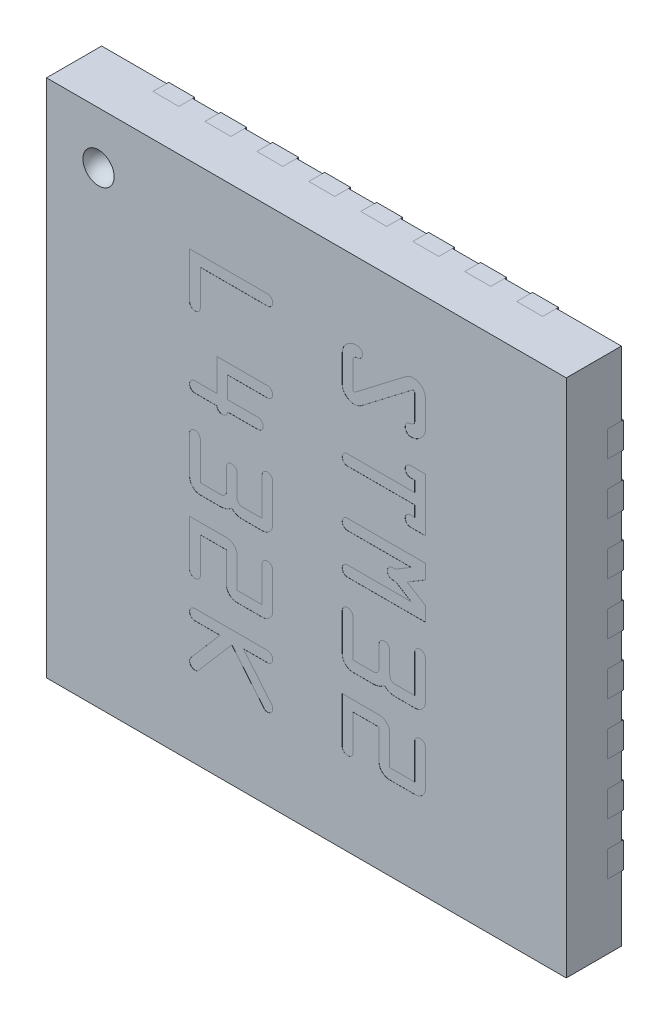
SolidWorks part; units mm, degrees
ref_plane "Спереди" through (0, 0, 0) normal (0, 0, 1) x (1, 0, 0)
ref_plane "Сверху" through (0, 0, 0) normal (0, 1, 0) x (1, 0, 0)
ref_plane "Справа" through (0, 0, 0) normal (1, 0, 0) x (0, 0, -1)
ref_plane "Плоскость1" through (0, 0, 0.02) normal (0, 0, 1) x (1, 0, 0)
sketch "Эскиз2" plane through (0, 0, 0.02) normal (0, 0, 1) x (1, 0, 0)
  line L1 (-2.5, -2.5) -> (2.5, -2.5)
  line L2 (-2.5, -2.5) -> (-2.5, 2.5)
  line L3 (-2.5, 2.5) -> (2.5, 2.5)
  line L4 (2.5, -2.5) -> (2.5, 2.5)
  line L5 (-2.5, -2.5) -> (2.5, 2.5) construction
  line L6 (-2.5, 2.5) -> (2.5, -2.5) construction
  point P0 (0, 0)
  dimension "D1" = 5
extrude "Бобышка-Вытянуть2" add sketch "Эскиз2" along normal blind 0.53 separate body
sketch "Эскиз1" plane through (0, 0, 0) normal (0, 0, 1) x (1, 0, 0)
  line L0 (0.125, 2.1) -> (0.375, 2.1) construction
  line L1 (-2.5, -2.5) -> (2.5, -2.5) construction
  line L2 (-2.5, -2.5) -> (-2.5, 2.5) construction
  line L3 (-2.5, 2.5) -> (2.5, 2.5) construction
  line L4 (2.5, -2.5) -> (2.5, 2.5) construction
  line L5 (-2.5, -2.5) -> (2.5, 2.5) construction
  line L6 (-2.5, 2.5) -> (2.5, -2.5) construction
  line L7 (0.625, 2.225) -> (0.625, 2.5)
  line L8 (0.125, 2.225) -> (0.125, 2.5)
  line L9 (0.125, 2.5) -> (0.375, 2.5)
  line L10 (0.375, 2.225) -> (0.375, 2.5)
  line L11 (0.125, 2.1) -> (0.375, 2.5) construction
  line L12 (0.125, 2.5) -> (0.375, 2.1) construction
  line L13 (0.625, 2.5) -> (0.875, 2.5)
  line L14 (0.875, 2.225) -> (0.875, 2.5)
  line L15 (0.625, 2.1) -> (0.875, 2.1) construction
  line L16 (0.625, 2.1) -> (0.875, 2.5) construction
  line L17 (0.625, 2.5) -> (0.875, 2.1) construction
  line L18 (1.125, 2.225) -> (1.125, 2.5)
  line L19 (1.125, 2.5) -> (1.375, 2.5)
  line L20 (1.375, 2.225) -> (1.375, 2.5)
  line L21 (1.125, 2.1) -> (1.375, 2.1) construction
  line L22 (1.125, 2.1) -> (1.375, 2.5) construction
  line L23 (1.125, 2.5) -> (1.375, 2.1) construction
  line L24 (1.625, 2.225) -> (1.625, 2.5)
  line L25 (1.625, 2.5) -> (1.875, 2.5)
  line L26 (1.875, 2.225) -> (1.875, 2.5)
  line L27 (1.625, 2.1) -> (1.875, 2.1) construction
  line L28 (1.625, 2.1) -> (1.875, 2.5) construction
  line L29 (1.625, 2.5) -> (1.875, 2.1) construction
  line L30 (2.225, -0.625) -> (2.5, -0.625)
  line L31 (2.225, -0.125) -> (2.5, -0.125)
  line L32 (2.5, -0.125) -> (2.5, -0.375)
  line L33 (2.225, -0.375) -> (2.5, -0.375)
  line L34 (2.5, -0.625) -> (2.5, -0.875)
  line L35 (2.225, -0.875) -> (2.5, -0.875)
  line L36 (2.225, -1.125) -> (2.5, -1.125)
  line L37 (2.5, -1.125) -> (2.5, -1.375)
  line L38 (2.225, -1.375) -> (2.5, -1.375)
  line L39 (2.225, -1.625) -> (2.5, -1.625)
  line L40 (2.5, -1.625) -> (2.5, -1.875)
  line L41 (2.225, -1.875) -> (2.5, -1.875)
  line L42 (0, -1000) -> (0, 49000) construction
  line L43 (-1000, 0) -> (49000, 0) construction
  line L44 (2.225, 1.875) -> (2.5, 1.875)
  line L45 (2.5, 1.625) -> (2.5, 1.875)
  line L46 (2.225, 1.625) -> (2.5, 1.625)
  line L47 (2.225, 1.375) -> (2.5, 1.375)
  line L48 (2.5, 1.125) -> (2.5, 1.375)
  line L49 (2.225, 1.125) -> (2.5, 1.125)
  line L50 (-1.625, 2.5) -> (-1.875, 2.1) construction
  line L51 (-1.625, 2.1) -> (-1.875, 2.5) construction
  line L52 (-1.625, 2.1) -> (-1.875, 2.1) construction
  line L53 (-1.125, 2.5) -> (-1.375, 2.1) construction
  line L54 (-1.125, 2.1) -> (-1.375, 2.5) construction
  line L55 (-1.125, 2.1) -> (-1.375, 2.1) construction
  line L56 (-0.625, 2.5) -> (-0.875, 2.1) construction
  line L57 (-0.625, 2.1) -> (-0.875, 2.5) construction
  line L58 (-0.625, 2.1) -> (-0.875, 2.1) construction
  line L59 (-0.125, 2.5) -> (-0.375, 2.1) construction
  line L60 (-0.125, 2.1) -> (-0.375, 2.5) construction
  line L61 (-0.125, 2.1) -> (-0.375, 2.1) construction
  line L62 (2.225, 0.875) -> (2.5, 0.875)
  line L63 (2.5, 0.625) -> (2.5, 0.875)
  line L64 (2.225, 0.375) -> (2.5, 0.375)
  line L65 (2.5, 0.125) -> (2.5, 0.375)
  line L66 (2.225, 0.125) -> (2.5, 0.125)
  line L67 (2.225, 0.625) -> (2.5, 0.625)
  line L68 (-1.875, 2.225) -> (-1.875, 2.5)
  line L69 (-1.625, 2.5) -> (-1.875, 2.5)
  line L70 (-1.625, 2.225) -> (-1.625, 2.5)
  line L71 (-1.375, 2.225) -> (-1.375, 2.5)
  line L72 (-1.125, 2.5) -> (-1.375, 2.5)
  line L73 (-1.125, 2.225) -> (-1.125, 2.5)
  line L74 (-0.875, 2.225) -> (-0.875, 2.5)
  line L75 (-0.625, 2.5) -> (-0.875, 2.5)
  line L76 (-0.375, 2.225) -> (-0.375, 2.5)
  line L77 (-0.125, 2.5) -> (-0.375, 2.5)
  line L78 (-0.125, 2.225) -> (-0.125, 2.5)
  line L79 (-0.625, 2.225) -> (-0.625, 2.5)
  line L80 (2.1, -0.125) -> (2.1, -0.375) construction
  line L81 (2.1, -0.125) -> (2.5, -0.375) construction
  line L82 (2.5, -0.125) -> (2.1, -0.375) construction
  line L83 (2.1, -0.625) -> (2.1, -0.875) construction
  line L84 (2.1, -0.625) -> (2.5, -0.875) construction
  line L85 (2.5, -0.625) -> (2.1, -0.875) construction
  line L86 (2.1, -1.125) -> (2.1, -1.375) construction
  line L87 (2.1, -1.125) -> (2.5, -1.375) construction
  line L88 (2.5, -1.125) -> (2.1, -1.375) construction
  line L89 (2.1, -1.625) -> (2.1, -1.875) construction
  line L90 (2.1, -1.625) -> (2.5, -1.875) construction
  line L91 (2.5, -1.625) -> (2.1, -1.875) construction
  line L92 (2.5, 1.625) -> (2.1, 1.875) construction
  line L93 (2.1, 1.625) -> (2.5, 1.875) construction
  line L94 (2.1, 1.625) -> (2.1, 1.875) construction
  line L95 (2.5, 1.125) -> (2.1, 1.375) construction
  line L96 (2.1, 1.125) -> (2.5, 1.375) construction
  line L97 (2.1, 1.125) -> (2.1, 1.375) construction
  line L98 (2.5, 0.625) -> (2.1, 0.875) construction
  line L99 (2.1, 0.625) -> (2.5, 0.875) construction
  line L100 (2.1, 0.625) -> (2.1, 0.875) construction
  line L101 (2.5, 0.125) -> (2.1, 0.375) construction
  line L102 (2.1, 0.125) -> (2.5, 0.375) construction
  line L103 (2.1, 0.125) -> (2.1, 0.375) construction
  line L104 (-0.625, -2.225) -> (-0.625, -2.5)
  line L105 (-0.125, -2.225) -> (-0.125, -2.5)
  line L106 (-0.125, -2.5) -> (-0.375, -2.5)
  line L107 (-0.375, -2.225) -> (-0.375, -2.5)
  line L108 (-0.625, -2.5) -> (-0.875, -2.5)
  line L109 (-0.875, -2.225) -> (-0.875, -2.5)
  line L110 (-1.125, -2.225) -> (-1.125, -2.5)
  line L111 (-1.125, -2.5) -> (-1.375, -2.5)
  line L112 (-1.375, -2.225) -> (-1.375, -2.5)
  line L113 (-1.625, -2.225) -> (-1.625, -2.5)
  line L114 (-1.625, -2.5) -> (-1.875, -2.5)
  line L115 (-1.875, -2.225) -> (-1.875, -2.5)
  line L116 (1.875, -2.225) -> (1.875, -2.5)
  line L117 (1.625, -2.5) -> (1.875, -2.5)
  line L118 (1.625, -2.225) -> (1.625, -2.5)
  line L119 (1.375, -2.225) -> (1.375, -2.5)
  line L120 (1.125, -2.5) -> (1.375, -2.5)
  line L121 (1.125, -2.225) -> (1.125, -2.5)
  line L122 (0.875, -2.225) -> (0.875, -2.5)
  line L123 (0.625, -2.5) -> (0.875, -2.5)
  line L124 (0.375, -2.225) -> (0.375, -2.5)
  line L125 (0.125, -2.5) -> (0.375, -2.5)
  line L126 (0.125, -2.225) -> (0.125, -2.5)
  line L127 (0.625, -2.225) -> (0.625, -2.5)
  line L128 (-0.125, -2.1) -> (-0.375, -2.1) construction
  line L129 (-0.125, -2.1) -> (-0.375, -2.5) construction
  line L130 (-0.125, -2.5) -> (-0.375, -2.1) construction
  line L131 (-0.625, -2.1) -> (-0.875, -2.1) construction
  line L132 (-0.625, -2.1) -> (-0.875, -2.5) construction
  line L133 (-0.625, -2.5) -> (-0.875, -2.1) construction
  line L134 (-1.125, -2.1) -> (-1.375, -2.1) construction
  line L135 (-1.125, -2.1) -> (-1.375, -2.5) construction
  line L136 (-1.125, -2.5) -> (-1.375, -2.1) construction
  line L137 (-1.625, -2.1) -> (-1.875, -2.1) construction
  line L138 (-1.625, -2.1) -> (-1.875, -2.5) construction
  line L139 (-1.625, -2.5) -> (-1.875, -2.1) construction
  line L140 (1.625, -2.5) -> (1.875, -2.1) construction
  line L141 (1.625, -2.1) -> (1.875, -2.5) construction
  line L142 (1.625, -2.1) -> (1.875, -2.1) construction
  line L143 (1.125, -2.5) -> (1.375, -2.1) construction
  line L144 (1.125, -2.1) -> (1.375, -2.5) construction
  line L145 (1.125, -2.1) -> (1.375, -2.1) construction
  line L146 (0.625, -2.5) -> (0.875, -2.1) construction
  line L147 (0.625, -2.1) -> (0.875, -2.5) construction
  line L148 (0.625, -2.1) -> (0.875, -2.1) construction
  line L149 (0.125, -2.5) -> (0.375, -2.1) construction
  line L150 (0.125, -2.1) -> (0.375, -2.5) construction
  line L151 (0.125, -2.1) -> (0.375, -2.1) construction
  line L152 (-2.225, 0.625) -> (-2.5, 0.625)
  line L153 (-2.225, 0.125) -> (-2.5, 0.125)
  line L154 (-2.5, 0.125) -> (-2.5, 0.375)
  line L155 (-2.225, 0.375) -> (-2.5, 0.375)
  line L156 (-2.5, 0.625) -> (-2.5, 0.875)
  line L157 (-2.225, 0.875) -> (-2.5, 0.875)
  line L158 (-2.225, 1.125) -> (-2.5, 1.125)
  line L159 (-2.5, 1.125) -> (-2.5, 1.375)
  line L160 (-2.225, 1.375) -> (-2.5, 1.375)
  line L161 (-2.225, 1.625) -> (-2.5, 1.625)
  line L162 (-2.5, 1.625) -> (-2.5, 1.875)
  line L163 (-2.225, 1.875) -> (-2.5, 1.875)
  line L164 (-2.225, -1.875) -> (-2.5, -1.875)
  line L165 (-2.5, -1.625) -> (-2.5, -1.875)
  line L166 (-2.225, -1.625) -> (-2.5, -1.625)
  line L167 (-2.225, -1.375) -> (-2.5, -1.375)
  line L168 (-2.5, -1.125) -> (-2.5, -1.375)
  line L169 (-2.225, -1.125) -> (-2.5, -1.125)
  line L170 (-2.225, -0.875) -> (-2.5, -0.875)
  line L171 (-2.5, -0.625) -> (-2.5, -0.875)
  line L172 (-2.225, -0.375) -> (-2.5, -0.375)
  line L173 (-2.5, -0.125) -> (-2.5, -0.375)
  line L174 (-2.225, -0.125) -> (-2.5, -0.125)
  line L175 (-2.225, -0.625) -> (-2.5, -0.625)
  line L176 (-2.1, 0.125) -> (-2.1, 0.375) construction
  line L177 (-2.1, 0.125) -> (-2.5, 0.375) construction
  line L178 (-2.5, 0.125) -> (-2.1, 0.375) construction
  line L179 (-2.1, 0.625) -> (-2.1, 0.875) construction
  line L180 (-2.1, 0.625) -> (-2.5, 0.875) construction
  line L181 (-2.5, 0.625) -> (-2.1, 0.875) construction
  line L182 (-2.1, 1.125) -> (-2.1, 1.375) construction
  line L183 (-2.1, 1.125) -> (-2.5, 1.375) construction
  line L184 (-2.5, 1.125) -> (-2.1, 1.375) construction
  line L185 (-2.1, 1.625) -> (-2.1, 1.875) construction
  line L186 (-2.1, 1.625) -> (-2.5, 1.875) construction
  line L187 (-2.5, 1.625) -> (-2.1, 1.875) construction
  line L188 (-2.5, -1.625) -> (-2.1, -1.875) construction
  line L189 (-2.1, -1.625) -> (-2.5, -1.875) construction
  line L190 (-2.1, -1.625) -> (-2.1, -1.875) construction
  line L191 (-2.5, -1.125) -> (-2.1, -1.375) construction
  line L192 (-2.1, -1.125) -> (-2.5, -1.375) construction
  line L193 (-2.1, -1.125) -> (-2.1, -1.375) construction
  line L194 (-2.5, -0.625) -> (-2.1, -0.875) construction
  line L195 (-2.1, -0.625) -> (-2.5, -0.875) construction
  line L196 (-2.1, -0.625) -> (-2.1, -0.875) construction
  line L197 (-2.5, -0.125) -> (-2.1, -0.375) construction
  line L198 (-2.1, -0.125) -> (-2.5, -0.375) construction
  line L199 (-2.1, -0.125) -> (-2.1, -0.375) construction
  arc A0 (0.125, 2.225) -> (0.375, 2.225) centre (0.25, 2.225) ccw
  arc A1 (0.625, 2.225) -> (0.875, 2.225) centre (0.75, 2.225) ccw
  arc A2 (1.125, 2.225) -> (1.375, 2.225) centre (1.25, 2.225) ccw
  arc A3 (1.625, 2.225) -> (1.875, 2.225) centre (1.75, 2.225) ccw
  arc A4 (2.225, -0.125) -> (2.225, -0.375) centre (2.225, -0.25) ccw
  arc A5 (2.225, -0.625) -> (2.225, -0.875) centre (2.225, -0.75) ccw
  arc A6 (2.225, -1.125) -> (2.225, -1.375) centre (2.225, -1.25) ccw
  arc A7 (2.225, -1.625) -> (2.225, -1.875) centre (2.225, -1.75) ccw
  arc A8 (-1.625, 2.225) -> (-1.875, 2.225) centre (-1.75, 2.225) cw
  arc A9 (-1.125, 2.225) -> (-1.375, 2.225) centre (-1.25, 2.225) cw
  arc A10 (-0.625, 2.225) -> (-0.875, 2.225) centre (-0.75, 2.225) cw
  arc A11 (-0.125, 2.225) -> (-0.375, 2.225) centre (-0.25, 2.225) cw
  arc A12 (2.225, 1.625) -> (2.225, 1.875) centre (2.225, 1.75) cw
  arc A13 (2.225, 1.125) -> (2.225, 1.375) centre (2.225, 1.25) cw
  arc A14 (2.225, 0.625) -> (2.225, 0.875) centre (2.225, 0.75) cw
  arc A15 (2.225, 0.125) -> (2.225, 0.375) centre (2.225, 0.25) cw
  arc A16 (-0.125, -2.225) -> (-0.375, -2.225) centre (-0.25, -2.225) ccw
  arc A17 (-0.625, -2.225) -> (-0.875, -2.225) centre (-0.75, -2.225) ccw
  arc A18 (-1.125, -2.225) -> (-1.375, -2.225) centre (-1.25, -2.225) ccw
  arc A19 (-1.625, -2.225) -> (-1.875, -2.225) centre (-1.75, -2.225) ccw
  arc A20 (1.625, -2.225) -> (1.875, -2.225) centre (1.75, -2.225) cw
  arc A21 (1.125, -2.225) -> (1.375, -2.225) centre (1.25, -2.225) cw
  arc A22 (0.625, -2.225) -> (0.875, -2.225) centre (0.75, -2.225) cw
  arc A23 (0.125, -2.225) -> (0.375, -2.225) centre (0.25, -2.225) cw
  arc A24 (-2.225, 0.125) -> (-2.225, 0.375) centre (-2.225, 0.25) ccw
  arc A25 (-2.225, 0.625) -> (-2.225, 0.875) centre (-2.225, 0.75) ccw
  arc A26 (-2.225, 1.125) -> (-2.225, 1.375) centre (-2.225, 1.25) ccw
  arc A27 (-2.225, 1.625) -> (-2.225, 1.875) centre (-2.225, 1.75) ccw
  arc A28 (-2.225, -1.625) -> (-2.225, -1.875) centre (-2.225, -1.75) cw
  arc A29 (-2.225, -1.125) -> (-2.225, -1.375) centre (-2.225, -1.25) cw
  arc A30 (-2.225, -0.625) -> (-2.225, -0.875) centre (-2.225, -0.75) cw
  arc A31 (-2.225, -0.125) -> (-2.225, -0.375) centre (-2.225, -0.25) cw
  point P0 (0, 0)
  point P5 (0.25, 2.3)
  point P13 (0.75, 2.3)
  point P23 (1.25, 2.3)
  point P31 (1.75, 2.3)
  point P42 (2.3, -0.25)
  point P48 (2.3, -0.75)
  point P61 (2.3, -1.25)
  point P85 (2.3, -1.75)
  point P102 (-1.75, 2.3)
  point P103 (-1.25, 2.3)
  point P104 (-0.75, 2.3)
  point P105 (-0.25, 2.3)
  point P137 (2.3, 1.75)
  point P138 (2.3, 1.25)
  point P139 (2.3, 0.75)
  point P140 (2.3, 0.25)
  point P141 (-0.25, -2.3)
  point P147 (-0.75, -2.3)
  point P157 (-1.25, -2.3)
  point P165 (-1.75, -2.3)
  point P201 (1.75, -2.3)
  point P202 (1.25, -2.3)
  point P203 (0.75, -2.3)
  point P204 (0.25, -2.3)
  point P205 (-2.3, 0.25)
  point P211 (-2.3, 0.75)
  point P221 (-2.3, 1.25)
  point P229 (-2.3, 1.75)
  point P265 (-2.3, -1.75)
  point P266 (-2.3, -1.25)
  point P267 (-2.3, -0.75)
  point P268 (-2.3, -0.25)
  point P269 (0, 0)
  point P397 (0, 0)
  dimension "D4" = 0.25
  dimension "D1" = 5
  dimension "D2" = 0.25
  dimension "D3" = 0.4
  dimension "D5" = 4
  dimension "D6" = 0.5
  dimension "D7" = 0.5
  dimension "D8" = 4
extrude "Вырез-Вытянуть1" cut sketch "Эскиз1" along normal blind 0.152
sketch "Эскиз3" plane through (0, 0, 0.152) normal (0, 0, -1) x (-1, 0, 0)
  line L138 (-1.875, 2.5) -> (-1.875, 2.225) construction
  line L139 (-1.625, 2.225) -> (-1.625, 2.5) construction
  line L140 (-1.625, 2.5) -> (-1.875, 2.5) construction
  line L141 (-1.375, 2.5) -> (-1.375, 2.225) construction
  line L142 (-1.125, 2.225) -> (-1.125, 2.5) construction
  line L143 (-1.125, 2.5) -> (-1.375, 2.5) construction
  line L144 (-0.875, 2.5) -> (-0.875, 2.225) construction
  line L145 (-0.625, 2.225) -> (-0.625, 2.5) construction
  line L146 (-0.625, 2.5) -> (-0.875, 2.5) construction
  line L147 (-0.375, 2.5) -> (-0.375, 2.225) construction
  line L148 (-0.125, 2.225) -> (-0.125, 2.5) construction
  line L149 (-0.125, 2.5) -> (-0.375, 2.5) construction
  line L150 (0.125, 2.5) -> (0.125, 2.225) construction
  line L151 (0.375, 2.225) -> (0.375, 2.5) construction
  line L152 (0.375, 2.5) -> (0.125, 2.5) construction
  line L153 (0.625, 2.5) -> (0.625, 2.225) construction
  line L154 (0.875, 2.225) -> (0.875, 2.5) construction
  line L155 (0.875, 2.5) -> (0.625, 2.5) construction
  line L156 (1.125, 2.5) -> (1.125, 2.225) construction
  line L157 (1.375, 2.225) -> (1.375, 2.5) construction
  line L158 (1.375, 2.5) -> (1.125, 2.5) construction
  line L159 (1.625, 2.5) -> (1.625, 2.225) construction
  line L160 (1.875, 2.225) -> (1.875, 2.5) construction
  line L161 (1.875, 2.5) -> (1.625, 2.5) construction
  line L162 (2.5, 1.875) -> (2.225, 1.875) construction
  line L163 (2.225, 1.625) -> (2.5, 1.625) construction
  line L164 (2.5, 1.625) -> (2.5, 1.875) construction
  line L165 (2.5, 1.375) -> (2.225, 1.375) construction
  line L166 (2.225, 1.125) -> (2.5, 1.125) construction
  line L167 (2.5, 1.125) -> (2.5, 1.375) construction
  line L168 (2.5, 0.875) -> (2.225, 0.875) construction
  line L169 (2.225, 0.625) -> (2.5, 0.625) construction
  line L170 (2.5, 0.625) -> (2.5, 0.875) construction
  line L171 (2.5, 0.375) -> (2.225, 0.375) construction
  line L172 (2.225, 0.125) -> (2.5, 0.125) construction
  line L173 (2.5, 0.125) -> (2.5, 0.375) construction
  line L174 (2.5, -0.125) -> (2.225, -0.125) construction
  line L175 (2.225, -0.375) -> (2.5, -0.375) construction
  line L176 (2.5, -0.375) -> (2.5, -0.125) construction
  line L177 (2.5, -0.625) -> (2.225, -0.625) construction
  line L178 (2.225, -0.875) -> (2.5, -0.875) construction
  line L179 (2.5, -0.875) -> (2.5, -0.625) construction
  line L180 (2.5, -1.125) -> (2.225, -1.125) construction
  line L181 (2.225, -1.375) -> (2.5, -1.375) construction
  line L182 (2.5, -1.375) -> (2.5, -1.125) construction
  line L183 (2.5, -1.625) -> (2.225, -1.625) construction
  line L184 (2.225, -1.875) -> (2.5, -1.875) construction
  line L185 (2.5, -1.875) -> (2.5, -1.625) construction
  line L186 (1.875, -2.5) -> (1.875, -2.225) construction
  line L187 (1.625, -2.225) -> (1.625, -2.5) construction
  line L188 (1.625, -2.5) -> (1.875, -2.5) construction
  line L189 (1.375, -2.5) -> (1.375, -2.225) construction
  line L190 (1.125, -2.225) -> (1.125, -2.5) construction
  line L191 (1.125, -2.5) -> (1.375, -2.5) construction
  line L192 (0.875, -2.5) -> (0.875, -2.225) construction
  line L193 (0.625, -2.225) -> (0.625, -2.5) construction
  line L194 (0.625, -2.5) -> (0.875, -2.5) construction
  line L195 (0.375, -2.5) -> (0.375, -2.225) construction
  line L196 (0.125, -2.225) -> (0.125, -2.5) construction
  line L197 (0.125, -2.5) -> (0.375, -2.5) construction
  line L198 (-0.125, -2.5) -> (-0.125, -2.225) construction
  line L199 (-0.375, -2.225) -> (-0.375, -2.5) construction
  line L200 (-0.375, -2.5) -> (-0.125, -2.5) construction
  line L201 (-0.625, -2.5) -> (-0.625, -2.225) construction
  line L202 (-0.875, -2.225) -> (-0.875, -2.5) construction
  line L203 (-0.875, -2.5) -> (-0.625, -2.5) construction
  line L204 (-1.125, -2.5) -> (-1.125, -2.225) construction
  line L205 (-1.375, -2.225) -> (-1.375, -2.5) construction
  line L206 (-1.375, -2.5) -> (-1.125, -2.5) construction
  line L207 (-1.625, -2.5) -> (-1.625, -2.225) construction
  line L208 (-1.875, -2.225) -> (-1.875, -2.5) construction
  line L209 (-1.875, -2.5) -> (-1.625, -2.5) construction
  line L210 (-2.5, -1.875) -> (-2.225, -1.875) construction
  line L211 (-2.225, -1.625) -> (-2.5, -1.625) construction
  line L212 (-2.5, -1.625) -> (-2.5, -1.875) construction
  line L213 (-2.5, -1.375) -> (-2.225, -1.375) construction
  line L214 (-2.225, -1.125) -> (-2.5, -1.125) construction
  line L215 (-2.5, -1.125) -> (-2.5, -1.375) construction
  line L216 (-2.5, -0.875) -> (-2.225, -0.875) construction
  line L217 (-2.225, -0.625) -> (-2.5, -0.625) construction
  line L218 (-2.5, -0.625) -> (-2.5, -0.875) construction
  line L219 (-2.5, -0.375) -> (-2.225, -0.375) construction
  line L220 (-2.225, -0.125) -> (-2.5, -0.125) construction
  line L221 (-2.5, -0.125) -> (-2.5, -0.375) construction
  line L222 (-2.5, 0.125) -> (-2.225, 0.125) construction
  line L223 (-2.225, 0.375) -> (-2.5, 0.375) construction
  line L224 (-2.5, 0.375) -> (-2.5, 0.125) construction
  line L225 (-2.5, 0.625) -> (-2.225, 0.625) construction
  line L226 (-2.225, 0.875) -> (-2.5, 0.875) construction
  line L227 (-2.5, 0.875) -> (-2.5, 0.625) construction
  line L228 (-2.5, 1.125) -> (-2.225, 1.125) construction
  line L229 (-2.225, 1.375) -> (-2.5, 1.375) construction
  line L230 (-2.5, 1.375) -> (-2.5, 1.125) construction
  line L231 (-2.5, 1.625) -> (-2.225, 1.625) construction
  line L232 (-2.225, 1.875) -> (-2.5, 1.875) construction
  line L233 (-2.5, 1.875) -> (-2.5, 1.625) construction
  line L234 (-1.875, 2.5) -> (-1.875, 2.225)
  line L235 (-1.625, 2.225) -> (-1.625, 2.5)
  line L236 (-1.625, 2.5) -> (-1.875, 2.5)
  line L237 (-1.375, 2.5) -> (-1.375, 2.225)
  line L238 (-1.125, 2.225) -> (-1.125, 2.5)
  line L239 (-1.125, 2.5) -> (-1.375, 2.5)
  line L240 (-0.875, 2.5) -> (-0.875, 2.225)
  line L241 (-0.625, 2.225) -> (-0.625, 2.5)
  line L242 (-0.625, 2.5) -> (-0.875, 2.5)
  line L243 (-0.375, 2.5) -> (-0.375, 2.225)
  line L244 (-0.125, 2.225) -> (-0.125, 2.5)
  line L245 (-0.125, 2.5) -> (-0.375, 2.5)
  line L246 (0.125, 2.5) -> (0.125, 2.225)
  line L247 (0.375, 2.225) -> (0.375, 2.5)
  line L248 (0.375, 2.5) -> (0.125, 2.5)
  line L249 (0.625, 2.5) -> (0.625, 2.225)
  line L250 (0.875, 2.225) -> (0.875, 2.5)
  line L251 (0.875, 2.5) -> (0.625, 2.5)
  line L252 (1.125, 2.5) -> (1.125, 2.225)
  line L253 (1.375, 2.225) -> (1.375, 2.5)
  line L254 (1.375, 2.5) -> (1.125, 2.5)
  line L255 (1.625, 2.5) -> (1.625, 2.225)
  line L256 (1.875, 2.225) -> (1.875, 2.5)
  line L257 (1.875, 2.5) -> (1.625, 2.5)
  line L258 (2.5, 1.875) -> (2.225, 1.875)
  line L259 (2.225, 1.625) -> (2.5, 1.625)
  line L260 (2.5, 1.625) -> (2.5, 1.875)
  line L261 (2.5, 1.375) -> (2.225, 1.375)
  line L262 (2.225, 1.125) -> (2.5, 1.125)
  line L263 (2.5, 1.125) -> (2.5, 1.375)
  line L264 (2.5, 0.875) -> (2.225, 0.875)
  line L265 (2.225, 0.625) -> (2.5, 0.625)
  line L266 (2.5, 0.625) -> (2.5, 0.875)
  line L267 (2.5, 0.375) -> (2.225, 0.375)
  line L268 (2.225, 0.125) -> (2.5, 0.125)
  line L269 (2.5, 0.125) -> (2.5, 0.375)
  line L270 (2.5, -0.125) -> (2.225, -0.125)
  line L271 (2.225, -0.375) -> (2.5, -0.375)
  line L272 (2.5, -0.375) -> (2.5, -0.125)
  line L273 (2.5, -0.625) -> (2.225, -0.625)
  line L274 (2.225, -0.875) -> (2.5, -0.875)
  line L275 (2.5, -0.875) -> (2.5, -0.625)
  line L282 (2.5, -1.125) -> (2.225, -1.125)
  line L283 (2.225, -1.375) -> (2.5, -1.375)
  line L284 (2.5, -1.375) -> (2.5, -1.125)
  line L285 (2.5, -1.625) -> (2.225, -1.625)
  line L286 (2.225, -1.875) -> (2.5, -1.875)
  line L287 (2.5, -1.875) -> (2.5, -1.625)
  line L288 (1.875, -2.5) -> (1.875, -2.225)
  line L289 (1.625, -2.225) -> (1.625, -2.5)
  line L290 (1.625, -2.5) -> (1.875, -2.5)
  line L291 (1.375, -2.5) -> (1.375, -2.225)
  line L292 (1.125, -2.225) -> (1.125, -2.5)
  line L293 (1.125, -2.5) -> (1.375, -2.5)
  line L294 (0.875, -2.5) -> (0.875, -2.225)
  line L295 (0.625, -2.225) -> (0.625, -2.5)
  line L296 (0.625, -2.5) -> (0.875, -2.5)
  line L297 (0.375, -2.5) -> (0.375, -2.225)
  line L298 (0.125, -2.225) -> (0.125, -2.5)
  line L299 (0.125, -2.5) -> (0.375, -2.5)
  line L300 (-0.125, -2.5) -> (-0.125, -2.225)
  line L301 (-0.375, -2.225) -> (-0.375, -2.5)
  line L302 (-0.375, -2.5) -> (-0.125, -2.5)
  line L303 (-0.625, -2.5) -> (-0.625, -2.225)
  line L304 (-0.875, -2.225) -> (-0.875, -2.5)
  line L305 (-0.875, -2.5) -> (-0.625, -2.5)
  line L306 (-1.125, -2.5) -> (-1.125, -2.225)
  line L307 (-1.375, -2.225) -> (-1.375, -2.5)
  line L308 (-1.375, -2.5) -> (-1.125, -2.5)
  line L309 (-1.625, -2.5) -> (-1.625, -2.225)
  line L310 (-1.875, -2.225) -> (-1.875, -2.5)
  line L311 (-1.875, -2.5) -> (-1.625, -2.5)
  line L312 (-2.5, -1.875) -> (-2.225, -1.875)
  line L313 (-2.225, -1.625) -> (-2.5, -1.625)
  line L314 (-2.5, -1.625) -> (-2.5, -1.875)
  line L315 (-2.5, -1.375) -> (-2.225, -1.375)
  line L316 (-2.225, -1.125) -> (-2.5, -1.125)
  line L317 (-2.5, -1.125) -> (-2.5, -1.375)
  line L318 (-2.5, -0.875) -> (-2.225, -0.875)
  line L319 (-2.225, -0.625) -> (-2.5, -0.625)
  line L320 (-2.5, -0.625) -> (-2.5, -0.875)
  line L321 (-2.5, -0.375) -> (-2.225, -0.375)
  line L322 (-2.225, -0.125) -> (-2.5, -0.125)
  line L323 (-2.5, -0.125) -> (-2.5, -0.375)
  line L324 (-2.5, 0.125) -> (-2.225, 0.125)
  line L325 (-2.225, 0.375) -> (-2.5, 0.375)
  line L326 (-2.5, 0.375) -> (-2.5, 0.125)
  line L327 (-2.5, 0.625) -> (-2.225, 0.625)
  line L328 (-2.225, 0.875) -> (-2.5, 0.875)
  line L329 (-2.5, 0.875) -> (-2.5, 0.625)
  line L330 (-2.5, 1.125) -> (-2.225, 1.125)
  line L331 (-2.225, 1.375) -> (-2.5, 1.375)
  line L332 (-2.5, 1.375) -> (-2.5, 1.125)
  line L333 (-2.5, 1.625) -> (-2.225, 1.625)
  line L334 (-2.225, 1.875) -> (-2.5, 1.875)
  line L335 (-2.5, 1.875) -> (-2.5, 1.625)
  arc A46 (-1.875, 2.225) -> (-1.625, 2.225) centre (-1.75, 2.225) ccw construction
  arc A47 (-1.375, 2.225) -> (-1.125, 2.225) centre (-1.25, 2.225) ccw construction
  arc A48 (-0.875, 2.225) -> (-0.625, 2.225) centre (-0.75, 2.225) ccw construction
  arc A49 (-0.375, 2.225) -> (-0.125, 2.225) centre (-0.25, 2.225) ccw construction
  arc A50 (0.125, 2.225) -> (0.375, 2.225) centre (0.25, 2.225) ccw construction
  arc A51 (0.625, 2.225) -> (0.875, 2.225) centre (0.75, 2.225) ccw construction
  arc A52 (1.125, 2.225) -> (1.375, 2.225) centre (1.25, 2.225) ccw construction
  arc A53 (1.625, 2.225) -> (1.875, 2.225) centre (1.75, 2.225) ccw construction
  arc A54 (2.225, 1.875) -> (2.225, 1.625) centre (2.225, 1.75) ccw construction
  arc A55 (2.225, 1.375) -> (2.225, 1.125) centre (2.225, 1.25) ccw construction
  arc A56 (2.225, 0.875) -> (2.225, 0.625) centre (2.225, 0.75) ccw construction
  arc A57 (2.225, 0.375) -> (2.225, 0.125) centre (2.225, 0.25) ccw construction
  arc A58 (2.225, -0.125) -> (2.225, -0.375) centre (2.225, -0.25) ccw construction
  arc A59 (2.225, -0.625) -> (2.225, -0.875) centre (2.225, -0.75) ccw construction
  arc A60 (2.225, -1.125) -> (2.225, -1.375) centre (2.225, -1.25) ccw construction
  arc A61 (2.225, -1.625) -> (2.225, -1.875) centre (2.225, -1.75) ccw construction
  arc A62 (1.875, -2.225) -> (1.625, -2.225) centre (1.75, -2.225) ccw construction
  arc A63 (1.375, -2.225) -> (1.125, -2.225) centre (1.25, -2.225) ccw construction
  arc A64 (0.875, -2.225) -> (0.625, -2.225) centre (0.75, -2.225) ccw construction
  arc A65 (0.375, -2.225) -> (0.125, -2.225) centre (0.25, -2.225) ccw construction
  arc A66 (-0.125, -2.225) -> (-0.375, -2.225) centre (-0.25, -2.225) ccw construction
  arc A67 (-0.625, -2.225) -> (-0.875, -2.225) centre (-0.75, -2.225) ccw construction
  arc A68 (-1.125, -2.225) -> (-1.375, -2.225) centre (-1.25, -2.225) ccw construction
  arc A69 (-1.625, -2.225) -> (-1.875, -2.225) centre (-1.75, -2.225) ccw construction
  arc A70 (-2.225, -1.875) -> (-2.225, -1.625) centre (-2.225, -1.75) ccw construction
  arc A71 (-2.225, -1.375) -> (-2.225, -1.125) centre (-2.225, -1.25) ccw construction
  arc A72 (-2.225, -0.875) -> (-2.225, -0.625) centre (-2.225, -0.75) ccw construction
  arc A73 (-2.225, -0.375) -> (-2.225, -0.125) centre (-2.225, -0.25) ccw construction
  arc A74 (-2.225, 0.125) -> (-2.225, 0.375) centre (-2.225, 0.25) ccw construction
  arc A75 (-2.225, 0.625) -> (-2.225, 0.875) centre (-2.225, 0.75) ccw construction
  arc A76 (-2.225, 1.125) -> (-2.225, 1.375) centre (-2.225, 1.25) ccw construction
  arc A77 (-2.225, 1.625) -> (-2.225, 1.875) centre (-2.225, 1.75) ccw construction
  arc A78 (-1.875, 2.225) -> (-1.625, 2.225) centre (-1.75, 2.225) ccw
  arc A79 (-1.375, 2.225) -> (-1.125, 2.225) centre (-1.25, 2.225) ccw
  arc A80 (-0.875, 2.225) -> (-0.625, 2.225) centre (-0.75, 2.225) ccw
  arc A81 (-0.375, 2.225) -> (-0.125, 2.225) centre (-0.25, 2.225) ccw
  arc A82 (0.125, 2.225) -> (0.375, 2.225) centre (0.25, 2.225) ccw
  arc A83 (0.625, 2.225) -> (0.875, 2.225) centre (0.75, 2.225) ccw
  arc A84 (1.125, 2.225) -> (1.375, 2.225) centre (1.25, 2.225) ccw
  arc A85 (1.625, 2.225) -> (1.875, 2.225) centre (1.75, 2.225) ccw
  arc A86 (2.225, 1.875) -> (2.225, 1.625) centre (2.225, 1.75) ccw
  arc A87 (2.225, 1.375) -> (2.225, 1.125) centre (2.225, 1.25) ccw
  arc A88 (2.225, 0.875) -> (2.225, 0.625) centre (2.225, 0.75) ccw
  arc A89 (2.225, 0.375) -> (2.225, 0.125) centre (2.225, 0.25) ccw
  arc A90 (2.225, -0.125) -> (2.225, -0.375) centre (2.225, -0.25) ccw
  arc A91 (2.225, -0.625) -> (2.225, -0.875) centre (2.225, -0.75) ccw
  arc A94 (2.225, -1.125) -> (2.225, -1.375) centre (2.225, -1.25) ccw
  arc A95 (2.225, -1.625) -> (2.225, -1.875) centre (2.225, -1.75) ccw
  arc A96 (1.875, -2.225) -> (1.625, -2.225) centre (1.75, -2.225) ccw
  arc A97 (1.375, -2.225) -> (1.125, -2.225) centre (1.25, -2.225) ccw
  arc A98 (0.875, -2.225) -> (0.625, -2.225) centre (0.75, -2.225) ccw
  arc A99 (0.375, -2.225) -> (0.125, -2.225) centre (0.25, -2.225) ccw
  arc A100 (-0.125, -2.225) -> (-0.375, -2.225) centre (-0.25, -2.225) ccw
  arc A101 (-0.625, -2.225) -> (-0.875, -2.225) centre (-0.75, -2.225) ccw
  arc A102 (-1.125, -2.225) -> (-1.375, -2.225) centre (-1.25, -2.225) ccw
  arc A103 (-1.625, -2.225) -> (-1.875, -2.225) centre (-1.75, -2.225) ccw
  arc A104 (-2.225, -1.875) -> (-2.225, -1.625) centre (-2.225, -1.75) ccw
  arc A105 (-2.225, -1.375) -> (-2.225, -1.125) centre (-2.225, -1.25) ccw
  arc A106 (-2.225, -0.875) -> (-2.225, -0.625) centre (-2.225, -0.75) ccw
  arc A107 (-2.225, -0.375) -> (-2.225, -0.125) centre (-2.225, -0.25) ccw
  arc A108 (-2.225, 0.125) -> (-2.225, 0.375) centre (-2.225, 0.25) ccw
  arc A109 (-2.225, 0.625) -> (-2.225, 0.875) centre (-2.225, 0.75) ccw
  arc A110 (-2.225, 1.125) -> (-2.225, 1.375) centre (-2.225, 1.25) ccw
  arc A111 (-2.225, 1.625) -> (-2.225, 1.875) centre (-2.225, 1.75) ccw
extrude "Бобышка-Вытянуть3" add sketch "Эскиз3" along normal blind 0.152 separate body
sketch "Эскиз5" plane through (0, 0, 0.02) normal (0, 0, -1) x (-1, 0, 0)
  line L0 (1.25, 1.75) -> (1.75, 1.25)
  line L1 (-1.65, -1.75) -> (1.65, -1.75)
  line L2 (-1.75, -1.65) -> (-1.75, 1.65)
  line L3 (-1.65, 1.75) -> (1.25, 1.75)
  line L4 (1.75, -1.65) -> (1.75, 1.25)
  line L5 (-1.75, -1.75) -> (1.75, 1.75) construction
  line L6 (-1.75, 1.75) -> (1.75, -1.75) construction
  arc A0 (1.65, -1.75) -> (1.75, -1.65) centre (1.65, -1.65) ccw
  arc A1 (-1.65, -1.75) -> (-1.75, -1.65) centre (-1.65, -1.65) cw
  arc A2 (-1.75, 1.65) -> (-1.65, 1.75) centre (-1.65, 1.65) cw
  point P0 (0, 0)
  dimension "D2" = 0.1
  dimension "D1" = 3.5
extrude "Бобышка-Вытянуть4" add sketch "Эскиз5" along normal up to surface (0.02 mm away) separate body up to face at (1.75, 2.3313, 0)
sketch "Эскиз6" plane through (0, 0, 0.55) normal (0, 0, 1) x (1, 0, 0)
  line L0 (2.5, 2.5) -> (-2.5, 2.5) construction
  line L1 (-2.5, 2.5) -> (-2.5, -2.5) construction
  circle A0 centre (-2, 2) radius 0.15
  dimension "D1" = 0.3
  dimension "D2" = 0.5
  dimension "D3" = 0.5
extrude "Вырез-Вытянуть2" cut sketch "Эскиз6" against normal blind 0.15
fillet "Скругление1" radius 0.15 1 edges at (-1.85, 2, 0.4)
sketch "Esquisse2" plane through (0, 0, 0.55) normal (0, 0, 1) x (1, 0, 0)
  line L0 (1.1446, 1.6506) -> (1.1446, 1.3924)
  line L1 (1.0417, 1.4083) -> (1.0417, 1.6437)
  line L2 (1.013, 1.6537) -> (0.5346, 1.2871)
  line L3 (0.3446, 1.3646) -> (0.3446, 1.6319)
  line L4 (0.4474, 1.6228) -> (0.4474, 1.3792)
  line L5 (0.476, 1.3708) -> (0.9546, 1.7376)
  line L6 (1.0028, 1.0206) -> (1.1446, 1.0206)
  line L7 (1.1446, 1.0206) -> (1.1446, 0.5063)
  line L8 (1.1446, 0.5063) -> (1.0024, 0.5063)
  line L9 (1.0033, 0.6092) -> (1.0417, 0.6092)
  line L10 (1.0417, 0.6092) -> (1.0417, 0.7121)
  line L11 (1.0417, 0.7121) -> (0.3951, 0.7121)
  line L12 (0.3951, 0.8149) -> (1.0417, 0.8149)
  line L13 (1.0417, 0.8149) -> (1.0417, 0.9178)
  line L14 (1.0417, 0.9178) -> (1.004, 0.9178)
  line L15 (0.8292, 0.0835) -> (0.8549, 0.0835)
  line L16 (0.8549, 0.0835) -> (1.0074, 0.1749)
  line L17 (1.0074, 0.1749) -> (0.3953, 0.1749)
  line L18 (0.3951, 0.2778) -> (1.1446, 0.2778)
  line L19 (1.1446, 0.2778) -> (1.1446, 0.1387)
  line L20 (1.1446, 0.1387) -> (0.9689, 0.0333)
  line L21 (0.9689, 0.0333) -> (1.1446, -0.0738)
  line L22 (1.1446, -0.0738) -> (1.1446, -0.2137)
  line L23 (1.1446, -0.2137) -> (0.3951, -0.2137)
  line L24 (0.3955, -0.1108) -> (1.0074, -0.1108)
  line L25 (1.0074, -0.1108) -> (0.8574, -0.0194)
  line L26 (0.8574, -0.0194) -> (0.8292, -0.0194)
  line L27 (1.0444, -0.9794) -> (0.8565, -0.9794)
  line L28 (0.6467, -0.9794) -> (0.4469, -0.9794)
  line L29 (0.3446, -0.8763) -> (0.3446, -0.516)
  line L30 (0.4474, -0.5162) -> (0.4474, -0.8765)
  line L31 (0.4474, -0.8765) -> (0.6467, -0.8765)
  line L32 (0.6989, -0.8253) -> (0.6989, -0.6192)
  line L33 (0.8017, -0.619) -> (0.8017, -0.8254)
  line L34 (0.851, -0.8765) -> (1.0417, -0.8765)
  line L35 (1.0417, -0.8765) -> (1.0417, -0.5156)
  line L36 (1.1446, -0.5158) -> (1.1446, -0.8779)
  line L37 (0.3446, -1.6506) -> (0.3446, -1.2079)
  line L38 (0.3446, -1.2079) -> (0.6981, -1.2079)
  line L39 (0.8017, -1.3042) -> (0.8017, -1.5965)
  line L40 (0.8017, -1.5965) -> (1.0417, -1.5965)
  line L41 (1.0417, -1.5965) -> (1.0417, -1.2556)
  line L42 (1.1446, -1.2563) -> (1.1446, -1.6015)
  line L43 (1.0444, -1.6994) -> (0.8003, -1.6994)
  line L44 (0.6989, -1.6022) -> (0.6989, -1.3108)
  line L45 (0.6989, -1.3108) -> (0.4474, -1.3108)
  line L46 (0.4474, -1.3108) -> (0.4474, -1.6513)
  line L47 (-1.124, 1.7635) -> (-0.3745, 1.7635)
  line L48 (-0.3744, 1.6606) -> (-1.0211, 1.6606)
  line L49 (-1.0211, 1.6606) -> (-1.0211, 1.3212)
  line L50 (-1.124, 1.3219) -> (-1.124, 1.7635)
  line L51 (-1.0731, 0.6892) -> (-0.8611, 0.6892)
  line L52 (-0.8611, 0.6892) -> (-0.8611, 0.9978)
  line L53 (-0.8611, 0.9978) -> (-0.3756, 0.9978)
  line L54 (-0.3754, 0.8949) -> (-0.7583, 0.8949)
  line L55 (-0.7583, 0.8949) -> (-0.7583, 0.6892)
  line L56 (-0.7583, 0.6892) -> (-0.4665, 0.6892)
  line L57 (-0.4665, 0.5863) -> (-0.7583, 0.5863)
  line L58 (-0.8611, 0.5863) -> (-1.0733, 0.5863)
  line L59 (-0.4242, -0.2365) -> (-0.612, -0.2365)
  line L60 (-0.8219, -0.2365) -> (-1.0217, -0.2365)
  line L61 (-1.124, -0.1335) -> (-1.124, 0.2269)
  line L62 (-1.0211, 0.2267) -> (-1.0211, -0.1337)
  line L63 (-1.0211, -0.1337) -> (-0.8219, -0.1337)
  line L64 (-0.7697, -0.0824) -> (-0.7697, 0.1237)
  line L65 (-0.6669, 0.1238) -> (-0.6669, -0.0826)
  line L66 (-0.6176, -0.1337) -> (-0.4269, -0.1337)
  line L67 (-0.4269, -0.1337) -> (-0.4269, 0.2272)
  line L68 (-0.324, 0.2271) -> (-0.324, -0.1351)
  line L69 (-1.124, -0.9078) -> (-1.124, -0.4651)
  line L70 (-1.124, -0.4651) -> (-0.7704, -0.4651)
  line L71 (-0.6669, -0.5613) -> (-0.6669, -0.8537)
  line L72 (-0.6669, -0.8537) -> (-0.4269, -0.8537)
  line L73 (-0.4269, -0.8537) -> (-0.4269, -0.5128)
  line L74 (-0.324, -0.5135) -> (-0.324, -0.8587)
  line L75 (-0.4242, -0.9565) -> (-0.6683, -0.9565)
  line L76 (-0.7697, -0.8594) -> (-0.7697, -0.5679)
  line L77 (-0.7697, -0.5679) -> (-1.0211, -0.5679)
  line L78 (-1.0211, -0.5679) -> (-1.0211, -0.9085)
  line L79 (-1.0735, -1.2079) -> (-0.3758, -1.2079)
  line L80 (-0.3733, -1.3108) -> (-0.6067, -1.3108)
  line L81 (-0.6067, -1.3108) -> (-0.3369, -1.6353)
  line L82 (-0.4092, -1.7062) -> (-0.7183, -1.3337)
  line L83 (-0.7183, -1.3337) -> (-1.0388, -1.7069)
  line L84 (-1.1102, -1.6342) -> (-0.8324, -1.3108)
  line L85 (-0.8324, -1.3108) -> (-1.0735, -1.3108)
  spline S0 degree 3 poles (1.1446, 1.3924) (1.1449, 1.3764) (1.1387, 1.3523) (1.1215, 1.3232) (1.1065, 1.306) (1.0929, 1.2928) (1.0816, 1.2843) (1.0698, 1.277) (1.0576, 1.271) (1.0447, 1.2662) (1.0266, 1.262) (1.0125, 1.2607) (1.003, 1.2606) knots 0 0 0 0 0.223175 0.342685 0.474746 0.542956 0.609369 0.673367 0.737868 0.801269 0.865945 1 1 1 1
  spline S1 degree 3 poles (1.003, 1.2606) (0.9961, 1.2608) (0.9854, 1.2625) (0.9733, 1.2699) (0.9655, 1.2772) (0.9587, 1.2855) (0.9525, 1.2978) (0.95, 1.3076) (0.9503, 1.3144) knots 0 0 0 0 0.251057 0.376315 0.507088 0.638599 0.75966 1 1 1 1
  spline S2 degree 3 poles (0.9503, 1.3144) (0.9503, 1.3223) (0.951, 1.3337) (0.9567, 1.3466) (0.9624, 1.3537) (0.9707, 1.3586) (0.9809, 1.3634) (0.9937, 1.3678) (1.0082, 1.3715) (1.0225, 1.3759) (1.0374, 1.3867) (1.0419, 1.3999) (1.0417, 1.4083) knots 0 0 0 0 0.165239 0.230107 0.287678 0.349691 0.427176 0.519651 0.629341 0.73661 0.826049 1 1 1 1
  spline S3 degree 3 poles (1.0417, 1.6437) (1.0416, 1.6477) (1.0413, 1.6567) (1.0334, 1.6609) (1.0299, 1.6606) knots 0 0 0 0 0.562294 1 1 1 1
  spline S4 degree 2 poles (1.0299, 1.6606) (1.0202, 1.6603) (1.013, 1.6537) knots 0 0 0 1 1 1
  spline S5 degree 3 poles (0.5346, 1.2871) (0.5237, 1.2786) (0.4998, 1.2653) (0.4728, 1.2605) (0.4596, 1.2606) knots 0 0 0 0 0.510227 1 1 1 1
  spline S6 degree 3 poles (0.4596, 1.2606) (0.4449, 1.2604) (0.423, 1.2647) (0.3966, 1.2782) (0.3789, 1.2923) (0.3639, 1.3084) (0.3493, 1.3317) (0.3444, 1.3514) (0.3446, 1.3646) knots 0 0 0 0 0.256865 0.385152 0.519387 0.651283 0.770685 1 1 1 1
  spline S7 degree 3 poles (0.3446, 1.6319) (0.3446, 1.6405) (0.346, 1.6533) (0.3502, 1.6699) (0.3551, 1.6816) (0.361, 1.693) (0.3685, 1.7039) (0.377, 1.7145) (0.3902, 1.7275) (0.4079, 1.7417) (0.4384, 1.7584) (0.4638, 1.7635) (0.4805, 1.7635) knots 0 0 0 0 0.124212 0.184487 0.245591 0.306533 0.369513 0.434688 0.50255 0.635575 0.760178 1 1 1 1
  spline S8 degree 3 poles (0.4805, 1.7635) (0.4891, 1.7634) (0.5014, 1.7622) (0.516, 1.7565) (0.5244, 1.7504) (0.5312, 1.7429) (0.5376, 1.7296) (0.5389, 1.7181) (0.5389, 1.7103) knots 0 0 0 0 0.285545 0.405068 0.516839 0.624561 0.739342 1 1 1 1
  spline S9 degree 3 poles (0.5389, 1.7103) (0.539, 1.7037) (0.537, 1.6939) (0.5302, 1.6826) (0.5235, 1.6751) (0.5156, 1.6686) (0.5037, 1.6623) (0.4937, 1.6606) (0.4871, 1.6606) knots 0 0 0 0 0.246992 0.366828 0.495754 0.625228 0.749854 1 1 1 1
  spline S10 degree 3 poles (0.4871, 1.6606) (0.4818, 1.6606) (0.4739, 1.6594) (0.4646, 1.6547) (0.4585, 1.6501) (0.4534, 1.6444) (0.449, 1.6353) (0.4472, 1.6279) (0.4474, 1.6228) knots 0 0 0 0 0.25837 0.38223 0.507013 0.630976 0.752235 1 1 1 1
  spline S11 degree 3 poles (0.4474, 1.3792) (0.4476, 1.3754) (0.4484, 1.3664) (0.4568, 1.3631) (0.4603, 1.3635) knots 0 0 0 0 0.535907 1 1 1 1
  spline S12 degree 2 poles (0.4603, 1.3635) (0.4694, 1.3643) (0.476, 1.3708) knots 0 0 0 1 1 1
  spline S13 degree 3 poles (0.9546, 1.7376) (0.9655, 1.7456) (0.989, 1.7593) (1.0159, 1.7634) (1.029, 1.7635) knots 0 0 0 0 0.508544 1 1 1 1
  spline S14 degree 3 poles (1.029, 1.7635) (1.0438, 1.7633) (1.0663, 1.7596) (1.0928, 1.7453) (1.1106, 1.731) (1.1255, 1.7136) (1.1406, 1.6877) (1.1446, 1.6653) (1.1446, 1.6506) knots 0 0 0 0 0.24873 0.371883 0.501018 0.62976 0.75261 1 1 1 1
  spline S15 degree 3 poles (1.0024, 0.5063) (0.9956, 0.5063) (0.9852, 0.508) (0.9732, 0.5147) (0.9653, 0.5213) (0.9587, 0.5291) (0.952, 0.5407) (0.9502, 0.5507) (0.9503, 0.5572) knots 0 0 0 0 0.255079 0.378601 0.507226 0.634154 0.755747 1 1 1 1
  spline S16 degree 3 poles (0.9503, 0.5572) (0.9504, 0.5639) (0.9522, 0.5741) (0.959, 0.5861) (0.9658, 0.5941) (0.9739, 0.6009) (0.9863, 0.607) (0.9964, 0.6096) (1.0033, 0.6092) knots 0 0 0 0 0.244621 0.369032 0.496899 0.626432 0.750711 1 1 1 1
  spline S17 degree 3 poles (0.3951, 0.7121) (0.3885, 0.7119) (0.3784, 0.7138) (0.3668, 0.7205) (0.359, 0.727) (0.3526, 0.7347) (0.3465, 0.7466) (0.3444, 0.7563) (0.3446, 0.7629) knots 0 0 0 0 0.2504 0.37394 0.502902 0.630431 0.751835 1 1 1 1
  spline S18 degree 3 poles (0.3446, 0.7629) (0.3444, 0.7699) (0.3464, 0.78) (0.3526, 0.7922) (0.359, 0.8001) (0.3667, 0.8067) (0.3785, 0.8131) (0.3884, 0.8151) (0.3951, 0.8149) knots 0 0 0 0 0.255674 0.37741 0.504942 0.632166 0.752973 1 1 1 1
  spline S19 degree 3 poles (1.004, 0.9178) (0.9969, 0.9175) (0.9865, 0.9197) (0.9738, 0.9258) (0.9657, 0.9325) (0.9588, 0.9403) (0.9523, 0.9523) (0.95, 0.9624) (0.9503, 0.9692) knots 0 0 0 0 0.255567 0.380968 0.508301 0.633702 0.754376 1 1 1 1
  spline S20 degree 3 poles (0.9503, 0.9692) (0.9502, 0.976) (0.952, 0.9861) (0.9586, 0.998) (0.9653, 1.0059) (0.9732, 1.0125) (0.9855, 1.0188) (0.9958, 1.0207) (1.0028, 1.0206) knots 0 0 0 0 0.247922 0.370044 0.495533 0.622701 0.745718 1 1 1 1
  spline S21 degree 3 poles (0.3953, 0.1749) (0.3886, 0.1747) (0.3787, 0.1767) (0.3669, 0.1831) (0.3592, 0.1897) (0.3527, 0.1975) (0.3464, 0.2095) (0.3444, 0.2195) (0.3446, 0.2263) knots 0 0 0 0 0.248274 0.369692 0.497558 0.624005 0.747382 1 1 1 1
  spline S22 degree 3 poles (0.3446, 0.2263) (0.3444, 0.2331) (0.3464, 0.2432) (0.3527, 0.2552) (0.3594, 0.2629) (0.3671, 0.2696) (0.3788, 0.2759) (0.3886, 0.2779) (0.3951, 0.2778) knots 0 0 0 0 0.253381 0.377131 0.505383 0.633636 0.75542 1 1 1 1
  spline S23 degree 3 poles (0.3951, -0.2137) (0.3884, -0.214) (0.3785, -0.2117) (0.3667, -0.2051) (0.359, -0.1983) (0.3526, -0.1904) (0.3465, -0.1784) (0.3444, -0.1685) (0.3446, -0.1617) knots 0 0 0 0 0.24853 0.370817 0.49991 0.627871 0.750017 1 1 1 1
  spline S24 degree 3 poles (0.3446, -0.1617) (0.3444, -0.1551) (0.3464, -0.1451) (0.3529, -0.1334) (0.3596, -0.1256) (0.3673, -0.1189) (0.3791, -0.1128) (0.3889, -0.1106) (0.3955, -0.1108) knots 0 0 0 0 0.247659 0.372903 0.501601 0.630299 0.754479 1 1 1 1
  spline S25 degree 3 poles (0.8292, -0.0194) (0.8227, -0.0195) (0.813, -0.0175) (0.8014, -0.011) (0.7937, -0.0042) (0.787, 0.0035) (0.7808, 0.0155) (0.7786, 0.0254) (0.7789, 0.0321) knots 0 0 0 0 0.243414 0.366765 0.49698 0.625743 0.749985 1 1 1 1
  spline S26 degree 3 poles (0.7789, 0.0321) (0.7787, 0.0388) (0.7807, 0.0489) (0.787, 0.0609) (0.7937, 0.0687) (0.8014, 0.0753) (0.813, 0.0815) (0.8227, 0.0837) (0.8292, 0.0835) knots 0 0 0 0 0.253922 0.377936 0.506462 0.634989 0.757033 1 1 1 1
  spline S27 degree 3 poles (0.8565, -0.9794) (0.8461, -0.9793) (0.8307, -0.9781) (0.8109, -0.9737) (0.7971, -0.9693) (0.7841, -0.9634) (0.7679, -0.9535) (0.7568, -0.9445) (0.7503, -0.9376) knots 0 0 0 0 0.267334 0.393514 0.516624 0.637066 0.757815 1 1 1 1
  spline S28 degree 3 poles (0.7503, -0.9376) (0.7428, -0.9445) (0.7306, -0.9532) (0.7137, -0.9633) (0.7008, -0.9692) (0.6877, -0.9737) (0.6697, -0.978) (0.6559, -0.9793) (0.6467, -0.9794) knots 0 0 0 0 0.266023 0.392841 0.516656 0.637282 0.757857 1 1 1 1
  spline S29 degree 3 poles (0.4469, -0.9794) (0.4337, -0.9792) (0.4135, -0.976) (0.3901, -0.9625) (0.3743, -0.9495) (0.3611, -0.9337) (0.3481, -0.9099) (0.3447, -0.8897) (0.3446, -0.8763) knots 0 0 0 0 0.24727 0.370363 0.498697 0.627031 0.750562 1 1 1 1
  spline S30 degree 3 poles (0.3446, -0.516) (0.3445, -0.5093) (0.3464, -0.4993) (0.3528, -0.4874) (0.3593, -0.4797) (0.3672, -0.4732) (0.3791, -0.4669) (0.3892, -0.4649) (0.396, -0.4651) knots 0 0 0 0 0.24987 0.37103 0.498625 0.624803 0.747918 1 1 1 1
  spline S31 degree 3 poles (0.396, -0.4651) (0.4028, -0.4649) (0.4129, -0.4669) (0.4248, -0.4732) (0.4327, -0.4797) (0.4393, -0.4875) (0.4456, -0.4994) (0.4476, -0.5094) (0.4474, -0.5162) knots 0 0 0 0 0.251589 0.374464 0.500396 0.627742 0.750617 1 1 1 1
  spline S32 degree 3 poles (0.6467, -0.8765) (0.6535, -0.8766) (0.6636, -0.8747) (0.6756, -0.8683) (0.6835, -0.8617) (0.6903, -0.854) (0.6969, -0.8421) (0.6991, -0.8321) (0.6989, -0.8253) knots 0 0 0 0 0.249892 0.371979 0.500201 0.628158 0.74937 1 1 1 1
  spline S33 degree 3 poles (0.6989, -0.6192) (0.6986, -0.6124) (0.7008, -0.6024) (0.7068, -0.5903) (0.7133, -0.5825) (0.7211, -0.5761) (0.7332, -0.5697) (0.7434, -0.5678) (0.7503, -0.5679) knots 0 0 0 0 0.250562 0.371917 0.497335 0.622753 0.745126 1 1 1 1
  spline S34 degree 3 poles (0.7503, -0.5679) (0.7571, -0.5678) (0.7672, -0.5698) (0.7791, -0.5761) (0.7869, -0.5826) (0.7936, -0.5903) (0.7998, -0.6023) (0.8019, -0.6123) (0.8017, -0.619) knots 0 0 0 0 0.251589 0.374464 0.500396 0.627742 0.750617 1 1 1 1
  spline S35 degree 3 poles (0.8017, -0.8254) (0.8017, -0.832) (0.8035, -0.8419) (0.8095, -0.8537) (0.8158, -0.8616) (0.8234, -0.8681) (0.8347, -0.8748) (0.8445, -0.8766) (0.851, -0.8765) knots 0 0 0 0 0.250107 0.374792 0.502229 0.630809 0.753668 1 1 1 1
  spline S36 degree 3 poles (1.0417, -0.5156) (1.0415, -0.509) (1.0436, -0.4991) (1.0499, -0.4872) (1.0565, -0.4796) (1.0643, -0.473) (1.0764, -0.467) (1.0863, -0.4649) (1.0931, -0.4651) knots 0 0 0 0 0.24853 0.370072 0.49807 0.624646 0.747122 1 1 1 1
  spline S37 degree 3 poles (1.0931, -0.4651) (1.0999, -0.4649) (1.11, -0.4669) (1.122, -0.4732) (1.1298, -0.4797) (1.1364, -0.4874) (1.1427, -0.4992) (1.1447, -0.5091) (1.1446, -0.5158) knots 0 0 0 0 0.252618 0.375995 0.502442 0.630308 0.751726 1 1 1 1
  spline S38 degree 3 poles (1.1446, -0.8779) (1.1447, -0.8913) (1.1412, -0.9113) (1.1284, -0.9348) (1.1153, -0.9501) (1.1001, -0.9631) (1.077, -0.976) (1.0574, -0.9795) (1.0444, -0.9794) knots 0 0 0 0 0.252537 0.37567 0.503755 0.63184 0.752994 1 1 1 1
  spline S39 degree 3 poles (0.6981, -1.2079) (0.7117, -1.2078) (0.7317, -1.2114) (0.7559, -1.2233) (0.7714, -1.2359) (0.785, -1.2504) (0.7978, -1.2728) (0.8019, -1.2916) (0.8017, -1.3042) knots 0 0 0 0 0.258025 0.38281 0.511765 0.639167 0.760087 1 1 1 1
  spline S40 degree 3 poles (1.0417, -1.2556) (1.0416, -1.2492) (1.0435, -1.2396) (1.0499, -1.2285) (1.0565, -1.2213) (1.0644, -1.2154) (1.0764, -1.2095) (1.0864, -1.208) (1.0931, -1.2079) knots 0 0 0 0 0.246218 0.365004 0.491232 0.616941 0.741649 1 1 1 1
  spline S41 degree 3 poles (1.0931, -1.2079) (1.0999, -1.208) (1.1099, -1.2095) (1.122, -1.2154) (1.1297, -1.2215) (1.1365, -1.2287) (1.1427, -1.2402) (1.1448, -1.2498) (1.1446, -1.2563) knots 0 0 0 0 0.256392 0.380154 0.506285 0.631555 0.75339 1 1 1 1
  spline S42 degree 3 poles (1.1446, -1.6015) (1.1447, -1.6143) (1.1412, -1.6336) (1.1282, -1.6561) (1.1154, -1.6711) (1.0999, -1.6834) (1.077, -1.6962) (1.0574, -1.6993) (1.0444, -1.6994) knots 0 0 0 0 0.247203 0.368649 0.49741 0.625736 0.748636 1 1 1 1
  spline S43 degree 3 poles (0.8003, -1.6994) (0.787, -1.6995) (0.7671, -1.696) (0.7434, -1.6838) (0.728, -1.6713) (0.7151, -1.6564) (0.7023, -1.6341) (0.6987, -1.6149) (0.6989, -1.6022) knots 0 0 0 0 0.255909 0.380784 0.508561 0.635159 0.756086 1 1 1 1
  spline S44 degree 3 poles (0.4474, -1.6513) (0.4476, -1.6576) (0.4456, -1.667) (0.4392, -1.678) (0.4326, -1.6853) (0.4248, -1.6916) (0.4128, -1.6977) (0.4028, -1.6994) (0.396, -1.6994) knots 0 0 0 0 0.239635 0.358493 0.486503 0.615085 0.74089 1 1 1 1
  spline S45 degree 3 poles (0.396, -1.6994) (0.3893, -1.6994) (0.3791, -1.6978) (0.3672, -1.6914) (0.3594, -1.6851) (0.3528, -1.6778) (0.3464, -1.6665) (0.3444, -1.657) (0.3446, -1.6506) knots 0 0 0 0 0.257182 0.3831 0.510725 0.637783 0.757728 1 1 1 1
  spline S46 degree 3 poles (-0.3745, 1.7635) (-0.368, 1.7635) (-0.3581, 1.7618) (-0.3467, 1.755) (-0.3389, 1.7485) (-0.3324, 1.7405) (-0.3258, 1.7288) (-0.3239, 1.7187) (-0.324, 1.7121) knots 0 0 0 0 0.245179 0.366397 0.494964 0.62525 0.750366 1 1 1 1
  spline S47 degree 3 poles (-0.324, 1.7121) (-0.3238, 1.7054) (-0.3259, 1.6955) (-0.3321, 1.6835) (-0.3389, 1.6758) (-0.3465, 1.6691) (-0.358, 1.6623) (-0.3678, 1.6606) (-0.3744, 1.6606) knots 0 0 0 0 0.249967 0.374185 0.502923 0.633114 0.754494 1 1 1 1
  spline S48 degree 3 poles (-1.0211, 1.3212) (-1.0209, 1.3147) (-1.0231, 1.3053) (-1.0293, 1.2938) (-1.036, 1.2865) (-1.0437, 1.28) (-1.0557, 1.2736) (-1.0658, 1.272) (-1.0726, 1.2721) knots 0 0 0 0 0.24145 0.362962 0.489589 0.618201 0.743691 1 1 1 1
  spline S49 degree 3 poles (-1.0726, 1.2721) (-1.0794, 1.2719) (-1.0894, 1.2739) (-1.1014, 1.2802) (-1.1092, 1.2867) (-1.1158, 1.2942) (-1.1221, 1.3057) (-1.1242, 1.3154) (-1.124, 1.3219) knots 0 0 0 0 0.255221 0.37987 0.50762 0.635092 0.755789 1 1 1 1
  spline S50 degree 3 poles (-0.3756, 0.9978) (-0.3688, 0.9981) (-0.3589, 0.9957) (-0.347, 0.9894) (-0.3392, 0.9826) (-0.3323, 0.9747) (-0.3258, 0.9626) (-0.3239, 0.9525) (-0.324, 0.9458) knots 0 0 0 0 0.248265 0.368329 0.497869 0.62741 0.752389 1 1 1 1
  spline S51 degree 3 poles (-0.324, 0.9458) (-0.3239, 0.9392) (-0.3258, 0.9293) (-0.3324, 0.9176) (-0.3392, 0.91) (-0.3469, 0.9032) (-0.3588, 0.8967) (-0.3688, 0.8948) (-0.3754, 0.8949) knots 0 0 0 0 0.246444 0.369128 0.49864 0.626707 0.751337 1 1 1 1
  spline S52 degree 3 poles (-0.4665, 0.6892) (-0.4598, 0.6893) (-0.4499, 0.6874) (-0.4381, 0.681) (-0.4304, 0.6744) (-0.4238, 0.6666) (-0.4172, 0.6547) (-0.4153, 0.6445) (-0.4154, 0.6378) knots 0 0 0 0 0.247595 0.368722 0.496284 0.623846 0.747984 1 1 1 1
  spline S53 degree 3 poles (-0.4154, 0.6378) (-0.4153, 0.631) (-0.4172, 0.6208) (-0.4238, 0.6089) (-0.4304, 0.6012) (-0.4381, 0.5945) (-0.4499, 0.5882) (-0.4598, 0.5862) (-0.4665, 0.5863) knots 0 0 0 0 0.252016 0.376154 0.503716 0.631278 0.752405 1 1 1 1
  spline S54 degree 3 poles (-0.7583, 0.5863) (-0.7582, 0.5803) (-0.7601, 0.5712) (-0.7665, 0.5606) (-0.7732, 0.5538) (-0.7809, 0.5478) (-0.793, 0.5423) (-0.803, 0.5406) (-0.8097, 0.5406) knots 0 0 0 0 0.23794 0.355342 0.480943 0.609444 0.735911 1 1 1 1
  spline S55 degree 3 poles (-0.8097, 0.5406) (-0.8165, 0.5406) (-0.8264, 0.5423) (-0.8385, 0.5478) (-0.8462, 0.5538) (-0.8529, 0.5606) (-0.8593, 0.5712) (-0.8612, 0.5803) (-0.8611, 0.5863) knots 0 0 0 0 0.264089 0.390556 0.519057 0.644658 0.76206 1 1 1 1
  spline S56 degree 3 poles (-1.0733, 0.5863) (-1.08, 0.5863) (-1.0901, 0.588) (-1.1019, 0.5947) (-1.1095, 0.6015) (-1.1161, 0.6092) (-1.122, 0.6213) (-1.1243, 0.631) (-1.124, 0.6378) knots 0 0 0 0 0.250584 0.373165 0.502568 0.629106 0.751545 1 1 1 1
  spline S57 degree 3 poles (-1.124, 0.6378) (-1.1242, 0.6446) (-1.1222, 0.6546) (-1.1158, 0.6666) (-1.1094, 0.6744) (-1.1017, 0.681) (-1.0898, 0.6874) (-1.0798, 0.6893) (-1.0731, 0.6892) knots 0 0 0 0 0.252082 0.375197 0.501375 0.62897 0.75013 1 1 1 1
  spline S58 degree 3 poles (-0.612, -0.2365) (-0.6225, -0.2365) (-0.6379, -0.2353) (-0.6577, -0.2309) (-0.6715, -0.2265) (-0.6845, -0.2205) (-0.7007, -0.2107) (-0.7117, -0.2016) (-0.7183, -0.1947) knots 0 0 0 0 0.267334 0.393514 0.516624 0.637066 0.757815 1 1 1 1
  spline S59 degree 3 poles (-0.7183, -0.1947) (-0.7257, -0.2016) (-0.738, -0.2103) (-0.7548, -0.2205) (-0.7677, -0.2263) (-0.7809, -0.2308) (-0.7988, -0.2351) (-0.8126, -0.2365) (-0.8219, -0.2365) knots 0 0 0 0 0.266023 0.392841 0.516656 0.637282 0.757857 1 1 1 1
  spline S60 degree 3 poles (-1.0217, -0.2365) (-1.0349, -0.2363) (-1.0551, -0.2331) (-1.0785, -0.2197) (-1.0943, -0.2066) (-1.1074, -0.1909) (-1.1205, -0.1671) (-1.1239, -0.1468) (-1.124, -0.1335) knots 0 0 0 0 0.24727 0.370363 0.498697 0.627031 0.750562 1 1 1 1
  spline S61 degree 3 poles (-1.124, 0.2269) (-1.1241, 0.2336) (-1.1222, 0.2436) (-1.1158, 0.2554) (-1.1092, 0.2631) (-1.1014, 0.2696) (-1.0894, 0.2759) (-1.0794, 0.2779) (-1.0726, 0.2778) knots 0 0 0 0 0.24987 0.37103 0.498625 0.624803 0.747918 1 1 1 1
  spline S62 degree 3 poles (-1.0726, 0.2778) (-1.0658, 0.2779) (-1.0557, 0.2759) (-1.0437, 0.2696) (-1.0359, 0.2631) (-1.0293, 0.2554) (-1.023, 0.2434) (-1.021, 0.2334) (-1.0211, 0.2267) knots 0 0 0 0 0.251589 0.374464 0.500396 0.627742 0.750617 1 1 1 1
  spline S63 degree 3 poles (-0.8219, -0.1337) (-0.8151, -0.1338) (-0.805, -0.1318) (-0.7929, -0.1255) (-0.7851, -0.1189) (-0.7783, -0.1112) (-0.7716, -0.0993) (-0.7695, -0.0892) (-0.7697, -0.0824) knots 0 0 0 0 0.249892 0.371979 0.500201 0.628158 0.74937 1 1 1 1
  spline S64 degree 3 poles (-0.7697, 0.1237) (-0.7699, 0.1305) (-0.7678, 0.1404) (-0.7618, 0.1525) (-0.7553, 0.1603) (-0.7475, 0.1667) (-0.7354, 0.1732) (-0.7252, 0.175) (-0.7183, 0.1749) knots 0 0 0 0 0.250562 0.371917 0.497335 0.622753 0.745126 1 1 1 1
  spline S65 degree 3 poles (-0.7183, 0.1749) (-0.7115, 0.1751) (-0.7014, 0.1731) (-0.6894, 0.1668) (-0.6816, 0.1603) (-0.675, 0.1525) (-0.6687, 0.1406) (-0.6667, 0.1306) (-0.6669, 0.1238) knots 0 0 0 0 0.251589 0.374464 0.500396 0.627742 0.750617 1 1 1 1
  spline S66 degree 3 poles (-0.6669, -0.0826) (-0.6669, -0.0892) (-0.6651, -0.099) (-0.6591, -0.1109) (-0.6528, -0.1187) (-0.6452, -0.1252) (-0.6338, -0.1319) (-0.624, -0.1338) (-0.6176, -0.1337) knots 0 0 0 0 0.250107 0.374792 0.502229 0.630809 0.753668 1 1 1 1
  spline S67 degree 3 poles (-0.4269, 0.2272) (-0.427, 0.2339) (-0.425, 0.2438) (-0.4187, 0.2556) (-0.4121, 0.2633) (-0.4043, 0.2698) (-0.3922, 0.2758) (-0.3822, 0.278) (-0.3754, 0.2778) knots 0 0 0 0 0.24853 0.370072 0.49807 0.624646 0.747122 1 1 1 1
  spline S68 degree 3 poles (-0.3754, 0.2778) (-0.3686, 0.2779) (-0.3586, 0.2759) (-0.3466, 0.2696) (-0.3388, 0.2631) (-0.3322, 0.2554) (-0.3258, 0.2436) (-0.3238, 0.2337) (-0.324, 0.2271) knots 0 0 0 0 0.252618 0.375995 0.502442 0.630308 0.751726 1 1 1 1
  spline S69 degree 3 poles (-0.324, -0.1351) (-0.3239, -0.1484) (-0.3274, -0.1684) (-0.3402, -0.192) (-0.3533, -0.2073) (-0.3685, -0.2202) (-0.3915, -0.2331) (-0.4112, -0.2366) (-0.4242, -0.2365) knots 0 0 0 0 0.252537 0.37567 0.503755 0.63184 0.752994 1 1 1 1
  spline S70 degree 3 poles (-0.7704, -0.4651) (-0.7569, -0.465) (-0.7369, -0.4686) (-0.7127, -0.4805) (-0.6971, -0.4931) (-0.6836, -0.5076) (-0.6708, -0.5299) (-0.6667, -0.5487) (-0.6669, -0.5613) knots 0 0 0 0 0.258025 0.38281 0.511765 0.639167 0.760087 1 1 1 1
  spline S71 degree 3 poles (-0.4269, -0.5128) (-0.427, -0.5063) (-0.4251, -0.4968) (-0.4186, -0.4856) (-0.4121, -0.4784) (-0.4042, -0.4725) (-0.3922, -0.4666) (-0.3821, -0.4652) (-0.3754, -0.4651) knots 0 0 0 0 0.246218 0.365004 0.491232 0.616941 0.741649 1 1 1 1
  spline S72 degree 3 poles (-0.3754, -0.4651) (-0.3687, -0.4651) (-0.3587, -0.4666) (-0.3466, -0.4725) (-0.3389, -0.4786) (-0.3321, -0.4858) (-0.3259, -0.4974) (-0.3237, -0.507) (-0.324, -0.5135) knots 0 0 0 0 0.256392 0.380154 0.506285 0.631555 0.75339 1 1 1 1
  spline S73 degree 3 poles (-0.324, -0.8587) (-0.3239, -0.8714) (-0.3274, -0.8908) (-0.3403, -0.9133) (-0.3532, -0.9282) (-0.3686, -0.9406) (-0.3915, -0.9533) (-0.4112, -0.9565) (-0.4242, -0.9565) knots 0 0 0 0 0.247203 0.368649 0.49741 0.625736 0.748636 1 1 1 1
  spline S74 degree 3 poles (-0.6683, -0.9565) (-0.6816, -0.9566) (-0.7015, -0.9531) (-0.7252, -0.9409) (-0.7406, -0.9284) (-0.7534, -0.9136) (-0.7662, -0.8912) (-0.7698, -0.8721) (-0.7697, -0.8594) knots 0 0 0 0 0.255909 0.380784 0.508561 0.635159 0.756086 1 1 1 1
  spline S75 degree 3 poles (-1.0211, -0.9085) (-1.021, -0.9147) (-1.023, -0.9241) (-1.0294, -0.9351) (-1.036, -0.9424) (-1.0437, -0.9487) (-1.0557, -0.9548) (-1.0658, -0.9566) (-1.0726, -0.9565) knots 0 0 0 0 0.239635 0.358493 0.486503 0.615085 0.74089 1 1 1 1
  spline S76 degree 3 poles (-1.0726, -0.9565) (-1.0793, -0.9565) (-1.0895, -0.955) (-1.1013, -0.9485) (-1.1092, -0.9423) (-1.1158, -0.9349) (-1.1221, -0.9237) (-1.1242, -0.9142) (-1.124, -0.9078) knots 0 0 0 0 0.257182 0.3831 0.510725 0.637783 0.757728 1 1 1 1
  spline S77 degree 3 poles (-0.3758, -1.2079) (-0.3689, -1.2078) (-0.3588, -1.2098) (-0.3467, -1.2161) (-0.339, -1.2228) (-0.3323, -1.2305) (-0.3257, -1.2424) (-0.3239, -1.2526) (-0.324, -1.2594) knots 0 0 0 0 0.251999 0.374044 0.500531 0.627017 0.750109 1 1 1 1
  spline S78 degree 3 poles (-0.324, -1.2594) (-0.324, -1.2661) (-0.3256, -1.2763) (-0.332, -1.2882) (-0.3383, -1.296) (-0.3456, -1.3027) (-0.3571, -1.3089) (-0.3668, -1.311) (-0.3733, -1.3108) knots 0 0 0 0 0.255545 0.380661 0.507474 0.633724 0.754873 1 1 1 1
  spline S79 degree 3 poles (-0.3369, -1.6353) (-0.3326, -1.6406) (-0.3256, -1.6525) (-0.3237, -1.6663) (-0.324, -1.6729) knots 0 0 0 0 0.505273 1 1 1 1
  spline S80 degree 3 poles (-0.324, -1.6729) (-0.324, -1.6795) (-0.3256, -1.6894) (-0.3324, -1.7008) (-0.3392, -1.7082) (-0.3471, -1.7143) (-0.3585, -1.7206) (-0.3683, -1.7222) (-0.3747, -1.7222) knots 0 0 0 0 0.251886 0.37333 0.502289 0.63209 0.7533 1 1 1 1
  spline S81 degree 3 poles (-0.3747, -1.7222) (-0.3811, -1.7223) (-0.3946, -1.7201) (-0.4049, -1.7111) (-0.4092, -1.7062) knots 0 0 0 0 0.493334 1 1 1 1
  spline S82 degree 3 poles (-1.0388, -1.7069) (-1.0427, -1.7118) (-1.0528, -1.7198) (-1.0653, -1.7224) (-1.0715, -1.7222) knots 0 0 0 0 0.503662 1 1 1 1
  spline S83 degree 3 poles (-1.0715, -1.7222) (-1.078, -1.7224) (-1.0879, -1.7203) (-1.0997, -1.7139) (-1.108, -1.7076) (-1.115, -1.7) (-1.1221, -1.6881) (-1.1239, -1.6778) (-1.124, -1.671) knots 0 0 0 0 0.241342 0.363454 0.493781 0.624684 0.747014 1 1 1 1
  spline S84 degree 3 poles (-1.124, -1.671) (-1.1239, -1.6644) (-1.1218, -1.6509) (-1.1146, -1.6393) (-1.1102, -1.6342) knots 0 0 0 0 0.494589 1 1 1 1
  spline S85 degree 3 poles (-1.0735, -1.3108) (-1.0801, -1.311) (-1.09, -1.309) (-1.1018, -1.3026) (-1.1095, -1.296) (-1.1161, -1.2883) (-1.122, -1.2761) (-1.1242, -1.2662) (-1.124, -1.2594) knots 0 0 0 0 0.24853 0.370072 0.49807 0.624646 0.747122 1 1 1 1
  spline S86 degree 3 poles (-1.124, -1.2594) (-1.1243, -1.2527) (-1.122, -1.2428) (-1.116, -1.2308) (-1.1096, -1.2229) (-1.1018, -1.2164) (-1.0901, -1.2097) (-1.0801, -1.2078) (-1.0735, -1.2079) knots 0 0 0 0 0.248913 0.371579 0.500084 0.62828 0.751087 1 1 1 1
  point P0 (0.7698, 0.2778)
extrude "Enlèv. mat.-Extru.1" cut sketch "Esquisse2" against normal blind 0.001
